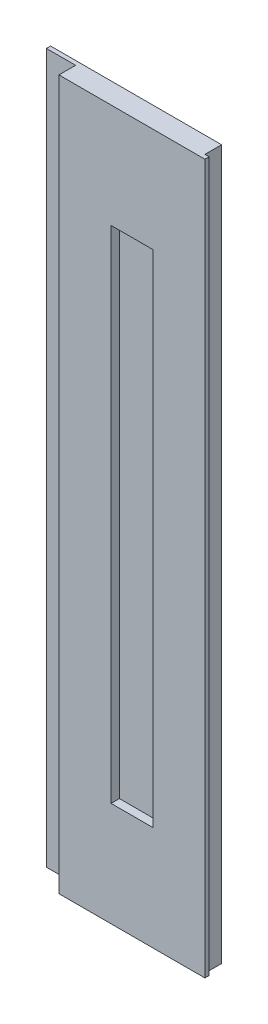
SolidWorks part; units mm, degrees
other "Markup1"
sketch "Sketch25" plane through (2, 18.9717, -1) normal (0.6328, -0.4558, -0.626) x (-0.6565, -0.7445, -0.1216)
material "ABS"
ref_plane "Alzado" through (0, 0, 0) normal (0, 0, 1) x (1, 0, 0)
ref_plane "Planta" through (0, 0, 0) normal (0, 1, 0) x (1, 0, 0)
ref_plane "Vista lateral" through (0, 0, 0) normal (1, 0, 0) x (0, 0, -1)
sketch "Sketch1" plane through (0, 0, 0) normal (0, 0, 1) x (1, 0, 0)
  line L1 (-14, 88.9717) -> (0, 88.9717)
  line L2 (-14, 88.9717) -> (-14, -11.0283)
  line L3 (-14, -11.0283) -> (0, -11.0283)
  line L4 (0, 88.9717) -> (0, -11.0283)
  line L5 (-14, 88.9717) -> (0, -11.0283) construction
  line L6 (-14, -11.0283) -> (0, 88.9717) construction
  point P0 (-7, 38.9717)
  dimension "D1" = 14
  dimension "D2" = 100
extrude "Boss-Extrude1" add sketch "Sketch1" along normal blind 2
sketch "Sketch2" plane through (0, 0, 2) normal (0, 0, 1) x (1, 0, 0)
  line L0 (-14, -11.0283) -> (0, -11.0283) construction
  line L1 (-14, 88.9717) -> (-12, 88.9717)
  line L2 (-14, 88.9717) -> (-14, -11.0283)
  line L3 (-14, -11.0283) -> (-12, -11.0283)
  line L4 (-12, 88.9717) -> (-12, -11.0283)
  line L5 (0, 88.9717) -> (-14, 88.9717) construction
  line L6 (0, -11.0283) -> (-2, -11.0283)
  line L7 (0, -11.0283) -> (0, 88.9717)
  line L8 (0, 88.9717) -> (-2, 88.9717)
  line L9 (-2, -11.0283) -> (-2, 88.9717)
  dimension "D1" = 2
  dimension "D2" = 2
extrude "Boss-Extrude2" add sketch "Sketch2" along normal blind 4
sketch "Sketch3" plane through (0, 0, 0) normal (1, 0, 0) x (0, 0, -1)
  line L1 (0, 88.9717) -> (-2, 88.9717)
  line L2 (0, 88.9717) -> (0, -11.0283)
  line L3 (0, -11.0283) -> (-2, -11.0283)
  line L4 (-2, 88.9717) -> (-2, -11.0283)
extrude "Boss-Extrude4" add sketch "Sketch3" along normal blind 2
sketch "Sketch4" plane through (-14, 0, 0) normal (-1, 0, 0) x (0, 0, 1)
  line L1 (0, 88.9717) -> (2, 88.9717)
  line L2 (0, 88.9717) -> (0, -11.0283)
  line L3 (0, -11.0283) -> (2, -11.0283)
  line L4 (2, 88.9717) -> (2, -11.0283)
extrude "Boss-Extrude5" add sketch "Sketch4" along normal blind 2
sketch "Sketch6" plane through (0, 0, 0) normal (0, 0, -1) x (-1, 0, 0)
  line L1 (16, -11.0283) -> (-2, -11.0283)
  line L2 (16, -11.0283) -> (16, 88.9717)
  line L3 (16, 88.9717) -> (-2, 88.9717)
  line L4 (-2, -11.0283) -> (-2, 88.9717)
extrude "Boss-Extrude6" add sketch "Sketch6" along normal blind 1
sketch "Sketch7" plane through (0, 0, -1) normal (0, 0, -1) x (-1, 0, 0)
  line L0 (-2, -11.0283) -> (16, -11.0283) construction
  line L1 (8.5, -11.0283) -> (5.5, -11.0283)
  line L2 (8.5, -11.0283) -> (8.5, 88.9717)
  line L3 (8.5, 88.9717) -> (5.5, 88.9717)
  line L4 (5.5, -11.0283) -> (5.5, 88.9717)
  line L5 (16, 88.9717) -> (-2, 88.9717) construction
  dimension "D1" = 3
  dimension "D2" = 7.5
extrude "Cut-Extrude1" cut sketch "Sketch7" against normal blind 1
sketch "Sketch8" plane through (0, 88.9717, 0) normal (0, 1, 0) x (1, 0, 0)
  line L0 (-2, -2) -> (-2, 1) construction
  line L1 (-5.5, 1) -> (2, 1) construction
  line L2 (2, 1) -> (-5.5, 1)
  line L12 (-5.5, 1) -> (-5.5, 0)
  line L13 (-5.5, 0) -> (-8.5, 0) construction
  line L14 (-5.5, 0) -> (-5.5, 1) construction
  line L15 (-5.5, 0) -> (-8.5, 0)
  line L16 (-8.5, 0) -> (-8.5, 1)
  line L17 (-8.5, 1) -> (-16, 1)
  line L18 (-16, 1) -> (-16, -2)
  line L19 (-16, -2) -> (-14, -2)
  line L20 (-14, -2) -> (-14, -6)
  line L21 (-14, -6) -> (-14, -2) construction
  line L22 (-14, -6) -> (-12, -6)
  line L23 (-12, -6) -> (-12, -2)
  line L24 (-12, -2) -> (-2, -2) construction
  line L25 (-12, -6) -> (-12, -2) construction
  line L26 (-12, -2) -> (-2, -2)
  line L27 (-2, -2) -> (-2, -6)
  line L28 (-2, -6) -> (0, -6)
  line L29 (0, -6) -> (0, -2)
  line L30 (0, -2) -> (2, -2)
  line L31 (2, -2) -> (2, 1)
extrude "Boss-Extrude7" add sketch "Sketch8" along normal blind 50
sketch "Sketch9" plane through (0, 138.9717, 0) normal (0, 1, 0) x (1, 0, 0)
  line L0 (-8.5, 1) -> (-16, 1) construction
  line L1 (-8.5, 1) -> (-11.5, 1)
  line L2 (-8.5, 1) -> (-8.5, 0)
  line L3 (-8.5, 0) -> (-11.5, 0)
  line L4 (-11.5, 1) -> (-11.5, 0)
  line L5 (-12, -2) -> (-12, 1) construction
  dimension "D1" = 3
  dimension "D2" = 1
  dimension "D3" = 0
extrude "Cut-Extrude2" cut sketch "Sketch9" against normal blind 150
sketch "Sketch10" plane through (0, 138.9717, 0) normal (0, 1, 0) x (1, 0, 0)
  line L0 (-5.5, 0) -> (-11.5, 0) construction
  line L1 (-5.5, 1) -> (-8.5, 1)
  line L2 (-5.5, 1) -> (-5.5, 0)
  line L3 (-5.5, 0) -> (-8.5, 0)
  line L4 (-8.5, 1) -> (-8.5, 0)
extrude "Boss-Extrude8" add sketch "Sketch10" against normal blind 150
sketch "Sketch11" plane through (0, 0, 2) normal (0, 0, 1) x (1, 0, 0)
  line L0 (-14, -11.0283) -> (-14, 138.9717) construction
  line L1 (-16, -11.0283) -> (-14, -11.0283)
  line L2 (-16, -11.0283) -> (-16, 38.9717)
  line L3 (-16, 38.9717) -> (-14, 38.9717)
  line L4 (-14, -11.0283) -> (-14, 38.9717)
  dimension "D1" = 50
extrude "Cut-Extrude3" cut sketch "Sketch11" against normal blind 50
sketch "Sketch14" plane through (0, 0, 6) normal (0, 0, 1) x (1, 0, 0)
  line L0 (2, 138.9717) -> (2, -11.0283) construction
  line L1 (-14, -11.0283) -> (2, -11.0283)
  line L2 (-14, -11.0283) -> (-14, 18.9717)
  line L3 (-14, 18.9717) -> (2, 18.9717)
  line L4 (2, -11.0283) -> (2, 18.9717)
  dimension "D1" = 30
extrude "Cut-Extrude4" cut sketch "Sketch14" against normal blind 50
sketch "Sketch15" plane through (0, 0, 2) normal (0, 0, 1) x (1, 0, 0)
  line L0 (-2, 138.9717) -> (-2, 18.9717) construction
  line L1 (-12, 138.9717) -> (-2, 138.9717)
  line L2 (-12, 138.9717) -> (-12, 136.9717)
  line L3 (-12, 136.9717) -> (-2, 136.9717)
  line L4 (-2, 138.9717) -> (-2, 136.9717)
  dimension "D1" = 2
extrude "Boss-Extrude9" add sketch "Sketch15" along normal blind 4
sketch "Sketch16" plane through (0, 0, 2) normal (0, 0, 1) x (1, 0, 0)
  line L0 (-2, 136.9717) -> (-2, 18.9717) construction
  line L1 (-12, 136.9717) -> (-2, 136.9717)
  line L2 (-12, 136.9717) -> (-12, 128.9717)
  line L3 (-12, 128.9717) -> (-2, 128.9717)
  line L4 (-2, 136.9717) -> (-2, 128.9717)
  dimension "D1" = 8
extrude "Boss-Extrude10" add sketch "Sketch16" along normal blind 4
sketch "Sketch21" plane through (0, 0, 6) normal (0, 0, 1) x (1, 0, 0)
  line L1 (-12, 128.9717) -> (-2, 128.9717)
  line L2 (-12, 128.9717) -> (-12, 136.9717)
  line L3 (-12, 136.9717) -> (-2, 136.9717)
  line L4 (-2, 128.9717) -> (-2, 136.9717)
  dimension "D1" = 8
extrude "Cut-Extrude5" cut sketch "Sketch21" against normal blind 4
sketch "Sketch23" plane through (0, 0, 6) normal (0, 0, 1) x (1, 0, 0)
  line L1 (2, 138.9717) -> (-14, 138.9717)
  line L2 (2, 138.9717) -> (2, 18.9717)
  line L3 (2, 18.9717) -> (-14, 18.9717)
  line L4 (-14, 138.9717) -> (-14, 18.9717)
extrude "Cut-Extrude7" cut sketch "Sketch23" against normal blind 2
sketch "Sketch24" plane through (0, 0, 0) normal (0, 0, -1) x (-1, 0, 0)
  line L0 (11.5, 18.9717) -> (11.5, 138.9717) construction
  line L1 (8.5, 138.9717) -> (11.5, 138.9717)
  line L2 (8.5, 138.9717) -> (8.5, 98.9717)
  line L3 (8.5, 98.9717) -> (11.5, 98.9717)
  line L4 (11.5, 138.9717) -> (11.5, 98.9717)
  dimension "D1" = 40
extrude "Boss-Extrude13" add sketch "Sketch24" along normal blind 1
sketch "Sketch26" plane through (0, 18.9717, 0) normal (0, -1, 0) x (1, 0, 0)
  line L0 (-14, 4) -> (-12, 4)
  line L1 (-12, 4) -> (-12, 2)
  line L2 (-12, 2) -> (-2, 2)
  line L3 (-2, 2) -> (-2, 4)
  line L4 (-2, 4) -> (0, 4)
  line L5 (0, 4) -> (0, 2)
  line L6 (0, 2) -> (2, 2)
  line L7 (2, 2) -> (2, -1)
  line L8 (2, -1) -> (-8.5, -1)
  line L9 (-8.5, -1) -> (-8.5, 0)
  line L10 (-8.5, 0) -> (-11.5, 0)
  line L11 (-11.5, 0) -> (-11.5, -1)
  line L12 (-11.5, 0) -> (-11.5, -1) construction
  line L13 (-11.5, -1) -> (-11.5, 0) construction
  line L14 (-11.5, -1) -> (-14, -1)
  line L15 (-14, -1) -> (-14, 4)
extrude "Boss-Extrude14" add sketch "Sketch26" along normal blind 50
sketch "Sketch27" plane through (0, 0, 0) normal (1, 0, 0) x (0, 0, -1)
  line L1 (-4, 138.9717) -> (-2, 138.9717)
  line L2 (-4, 138.9717) -> (-4, -31.0283)
  line L3 (-4, -31.0283) -> (-2, -31.0283)
  line L4 (-2, 138.9717) -> (-2, -31.0283)
extrude "Boss-Extrude15" add sketch "Sketch27" along normal through all
sketch "Sketch28" plane through (2, 0, 0) normal (1, 0, 0) x (0, 0, -1)
  line L1 (-4, 138.9717) -> (1, 138.9717)
  line L2 (-4, 138.9717) -> (-4, -31.0283)
  line L3 (-4, -31.0283) -> (1, -31.0283)
  line L4 (1, 138.9717) -> (1, -31.0283)
extrude "Boss-Extrude16" add sketch "Sketch28" along normal blind 18
sketch "Sketch29" plane through (20, 0, 0) normal (1, 0, 0) x (0, 0, -1)
  line L1 (-4, 138.9717) -> (1, 138.9717)
  line L2 (-4, 138.9717) -> (-4, -31.0283)
  line L3 (-4, -31.0283) -> (1, -31.0283)
  line L4 (1, 138.9717) -> (1, -31.0283)
extrude "Boss-Extrude17" add sketch "Sketch29" against normal blind 40
sketch "Sketch30" plane through (-20, 0, 0) normal (-1, 0, 0) x (0, 0, 1)
  line L0 (-1, 138.9717) -> (4, 138.9717) construction
  line L1 (4, -31.0283) -> (3, -31.0283)
  line L2 (4, -31.0283) -> (4, 138.9717)
  line L3 (4, 138.9717) -> (3, 138.9717)
  line L4 (3, -31.0283) -> (3, 138.9717)
  dimension "D1" = 1
extrude "Boss-Extrude18" add sketch "Sketch30" along normal blind 1
sketch "Sketch31" plane through (20, 0, 0) normal (1, 0, 0) x (0, 0, -1)
  line L0 (1, 138.9717) -> (-4, 138.9717) construction
  line L1 (-4, -31.0283) -> (-3, -31.0283)
  line L2 (-4, -31.0283) -> (-4, 138.9717)
  line L3 (-4, 138.9717) -> (-3, 138.9717)
  line L4 (-3, -31.0283) -> (-3, 138.9717)
  dimension "D1" = 1
extrude "Boss-Extrude19" add sketch "Sketch31" along normal blind 1
sketch "Sketch32" plane through (0, 0, -1) normal (0, 0, -1) x (-1, 0, 0)
  line L0 (20, -31.0283) -> (5, -31.0283) construction
  line L1 (20, -31.0283) -> (-20, -31.0283) construction
  line L2 (-20, 138.9717) -> (20, 138.9717) construction
  line L3 (5, -31.0283) -> (-5, -31.0283)
  line L4 (5, -31.0283) -> (5, 138.9717)
  line L5 (5, 138.9717) -> (-5, 138.9717)
  line L6 (-5, -31.0283) -> (-5, 138.9717)
  dimension "D1" = 15
  dimension "D2" = 10
extrude "Cut-Extrude8" cut sketch "Sketch32" against normal blind 2
sketch "Sketch33" plane through (0, 138.9717, 0) normal (0, 1, 0) x (1, 0, 0)
  line L1 (-20, 1) -> (20, 1)
  line L2 (-20, 1) -> (-20, -3)
  line L3 (-20, -3) -> (20, -3)
  line L4 (20, 1) -> (20, -3)
extrude "Boss-Extrude20" add sketch "Sketch33" against normal blind 1
sketch "Sketch34" plane through (0, 0, 1) normal (0, 0, -1) x (-1, 0, 0)
  line L0 (-5, 137.9717) -> (-5, -31.0283) construction
  line L1 (5, -31.0283) -> (-5, -31.0283)
  line L2 (5, -31.0283) -> (5, 8.9717)
  line L3 (5, 8.9717) -> (-5, 8.9717)
  line L4 (-5, -31.0283) -> (-5, 8.9717)
  dimension "D1" = 40
extrude "Boss-Extrude21" add sketch "Sketch34" along normal through all
sketch "Sketch35" plane through (0, 0, 4) normal (0, 0, 1) x (1, 0, 0)
  line L0 (-21, -31.0283) -> (-20, -31.0283) construction
  line L1 (21, -31.0283) -> (-21, -31.0283) construction
  line L2 (21, 138.9717) -> (-21, 138.9717) construction
  line L3 (-19.5, -31.0283) -> (-16.5, -31.0283)
  line L4 (-19.5, -31.0283) -> (-19.5, 138.9717)
  line L5 (-19.5, 138.9717) -> (-16.5, 138.9717)
  line L6 (-16.5, -31.0283) -> (-16.5, 138.9717)
  dimension "D1" = 1
  dimension "D2" = 3
  dimension "D3" = 0.5
extrude "Cut-Extrude9" cut sketch "Sketch35" against normal blind 1
sketch "Sketch36" plane through (-20, 0, 0) normal (-1, 0, 0) x (0, 0, 1)
  line L0 (-1, 138.9717) -> (3, 138.9717) construction
  line L1 (-1, -31.0283) -> (0, -31.0283)
  line L2 (-1, -31.0283) -> (-1, 138.9717)
  line L3 (-1, 138.9717) -> (0, 138.9717)
  line L4 (0, -31.0283) -> (0, 138.9717)
  dimension "D1" = 1
extrude "Boss-Extrude22" add sketch "Sketch36" along normal blind 1
sketch "Sketch37" plane through (0, 0, 3) normal (0, 0, -1) x (-1, 0, 0)
  line L1 (20, -31.0283) -> (21, -31.0283)
  line L2 (20, -31.0283) -> (20, 138.9717)
  line L3 (20, 138.9717) -> (21, 138.9717)
  line L4 (21, -31.0283) -> (21, 138.9717)
extrude "Cut-Extrude10" cut sketch "Sketch37" against normal through all
sketch "Sketch39" plane through (0, 0, 4) normal (0, 0, 1) x (1, 0, 0)
  line L0 (21, 138.9717) -> (-16.5, 138.9717) construction
  line L1 (-20, -31.0283) -> (-14, -31.0283)
  line L2 (-20, -31.0283) -> (-20, 138.9717)
  line L3 (-20, 138.9717) -> (-14, 138.9717)
  line L4 (-14, -31.0283) -> (-14, 138.9717)
  dimension "D1" = 6
extrude "Cut-Extrude11" cut sketch "Sketch39" against normal blind 4 contours L2 L1 L4 L3
sketch "Sketch40" plane through (0, 0, 1) normal (0, 0, -1) x (-1, 0, 0)
  line L1 (-5, 137.9717) -> (5, 137.9717)
  line L2 (-5, 137.9717) -> (-5, 8.9717)
  line L3 (-5, 8.9717) -> (5, 8.9717)
  line L4 (5, 137.9717) -> (5, 8.9717)
extrude "Boss-Extrude23" add sketch "Sketch40" along normal through all
sketch "Sketch41" plane through (0, 0, 4) normal (0, 0, 1) x (1, 0, 0)
  line L0 (21, 138.9717) -> (20, 138.9717) construction
  line L1 (21, 138.9717) -> (-14, 138.9717) construction
  line L2 (20, 138.9717) -> (5, 138.9717) construction
  line L3 (5, 138.9717) -> (5, 98.9717) construction
  line L5 (5, 98.9717) -> (-5, 98.9717)
  line L6 (5, 98.9717) -> (5, -21.0283)
  line L7 (5, -21.0283) -> (-5, -21.0283)
  line L8 (-5, 98.9717) -> (-5, -21.0283)
  dimension "D1" = 1
  dimension "D2" = 40
  dimension "D3" = 120
  dimension "D4" = 10
extrude "Cut-Extrude12" cut sketch "Sketch41" against normal blind 2
sketch "Sketch43" plane through (0, -31.0283, 0) normal (0, -1, 0) x (1, 0, 0)
  line L0 (-21, -1) -> (-21, 0)
  line L1 (-21, 0) -> (-14, 0)
  line L2 (-14, 0) -> (-14, 4)
  line L3 (-14, 4) -> (21, 4)
  line L4 (21, 4) -> (21, 3)
  line L5 (21, 3) -> (20, 3)
  line L6 (20, 3) -> (20, -1)
  line L7 (20, -1) -> (-21, -1)
extrude "Boss-Extrude24" add sketch "Sketch43" along normal blind 30
sketch "Sketch44" plane through (0, 138.9717, 0) normal (0, 1, 0) x (1, 0, 0)
  line L0 (-21, 1) -> (20, 1)
  line L1 (20, 1) -> (20, -3)
  line L2 (20, -3) -> (21, -3)
  line L3 (21, -3) -> (21, -4)
  line L4 (21, -4) -> (-14, -4)
  line L5 (-14, -4) -> (-14, 0)
  line L6 (-14, 0) -> (-21, 0)
  line L7 (-21, 0) -> (-21, 1)
extrude "Cut-Extrude13" cut sketch "Sketch44" against normal blind 30
sketch "Sketch45" plane through (0, 0, 4) normal (0, 0, 1) x (1, 0, 0)
  line L0 (3.5, -61.0283) -> (3.5, -38.8705) construction
  line L1 (21, -61.0283) -> (-14, -61.0283) construction
  line L2 (21, 108.9717) -> (21, 78.9717) construction
  line L3 (21, 108.9717) -> (21, -61.0283) construction
  line L4 (5, -21.0283) -> (5, 98.9717) construction
  line L5 (5, 78.9717) -> (-5, 78.9717)
  line L6 (5, 78.9717) -> (5, -41.0283)
  line L7 (5, -41.0283) -> (-5, -41.0283)
  line L8 (-5, 78.9717) -> (-5, -41.0283)
  line L9 (-5, 98.9717) -> (-5, -21.0283) construction
  line L10 (-14, 108.9717) -> (21, 108.9717) construction
  dimension "D1" = 30
  dimension "D2" = 30
  dimension "D3" = 120
extrude "Cut-Extrude14" cut sketch "Sketch45" against normal blind 2
sketch "Sketch46" plane through (0, 0, 4) normal (0, 0, 1) x (1, 0, 0)
  line L0 (5, -41.0283) -> (5, 78.9717) construction
  line L1 (5, -41.0283) -> (5, 98.9717) construction
  line L3 (5, 78.9717) -> (-5, 78.9717)
  line L4 (5, 78.9717) -> (5, 98.9717)
  line L5 (5, 98.9717) -> (-5, 98.9717)
  line L6 (-5, 78.9717) -> (-5, 98.9717)
  dimension "D1" = 120
extrude "Boss-Extrude25" add sketch "Sketch46" against normal blind 2
sketch "Sketch47" plane through (0, 0, 4) normal (0, 0, 1) x (1, 0, 0)
  line L0 (3.5, -61.0283) -> (3.5, -36.0283) construction
  line L3 (3.5, 108.9717) -> (3.5, 83.9717) construction
  line L4 (-14, 108.9717) -> (21, 108.9717) construction
  line L5 (21, -61.0283) -> (-14, -61.0283) construction
  line L6 (-5, 78.9717) -> (-5, -41.0283) construction
  line L7 (-5, -36.0283) -> (5, -36.0283)
  line L8 (-5, -36.0283) -> (-5, -41.0283)
  line L9 (-5, -41.0283) -> (5, -41.0283)
  line L10 (5, -36.0283) -> (5, -41.0283)
  dimension "D1" = 25
  dimension "D2" = 25
extrude "Boss-Extrude26" add sketch "Sketch47" against normal blind 2
sketch "Sketch48" plane through (0, 0, 4) normal (0, 0, 1) x (1, 0, 0)
  line L1 (-5, 78.9717) -> (5, 78.9717)
  line L2 (-5, 78.9717) -> (-5, 83.9717)
  line L3 (-5, 83.9717) -> (5, 83.9717)
  line L4 (5, 78.9717) -> (5, 83.9717)
  dimension "D1" = 5
extrude "Cut-Extrude15" cut sketch "Sketch48" against normal blind 2
sketch "Sketch52" plane through (0, 0, 4) normal (0, 0, 1) x (1, 0, 0)
  line L1 (-5, 83.9717) -> (5, 83.9717)
  line L2 (-5, 83.9717) -> (-5, -36.0283)
  line L3 (-5, -36.0283) -> (5, -36.0283)
  line L4 (5, 83.9717) -> (5, -36.0283)
extrude "Boss-Extrude27" add sketch "Sketch52" against normal blind 2
sketch "Sketch53" plane through (0, 0, 4) normal (0, 0, 1) x (1, 0, 0)
  line L0 (21, -61.0283) -> (-14, -61.0283) construction
  line L1 (-1.5, 83.9717) -> (8.5, 83.9717)
  line L2 (-1.5, 83.9717) -> (-1.5, -36.0283)
  line L3 (-1.5, -36.0283) -> (8.5, -36.0283)
  line L4 (8.5, 83.9717) -> (8.5, -36.0283)
  line L5 (21, 108.9717) -> (21, -61.0283) construction
  dimension "D1" = 120
  dimension "D2" = 10
  dimension "D3" = 25
  dimension "D4" = 12.5
extrude "Cut-Extrude16" cut sketch "Sketch53" against normal blind 2
